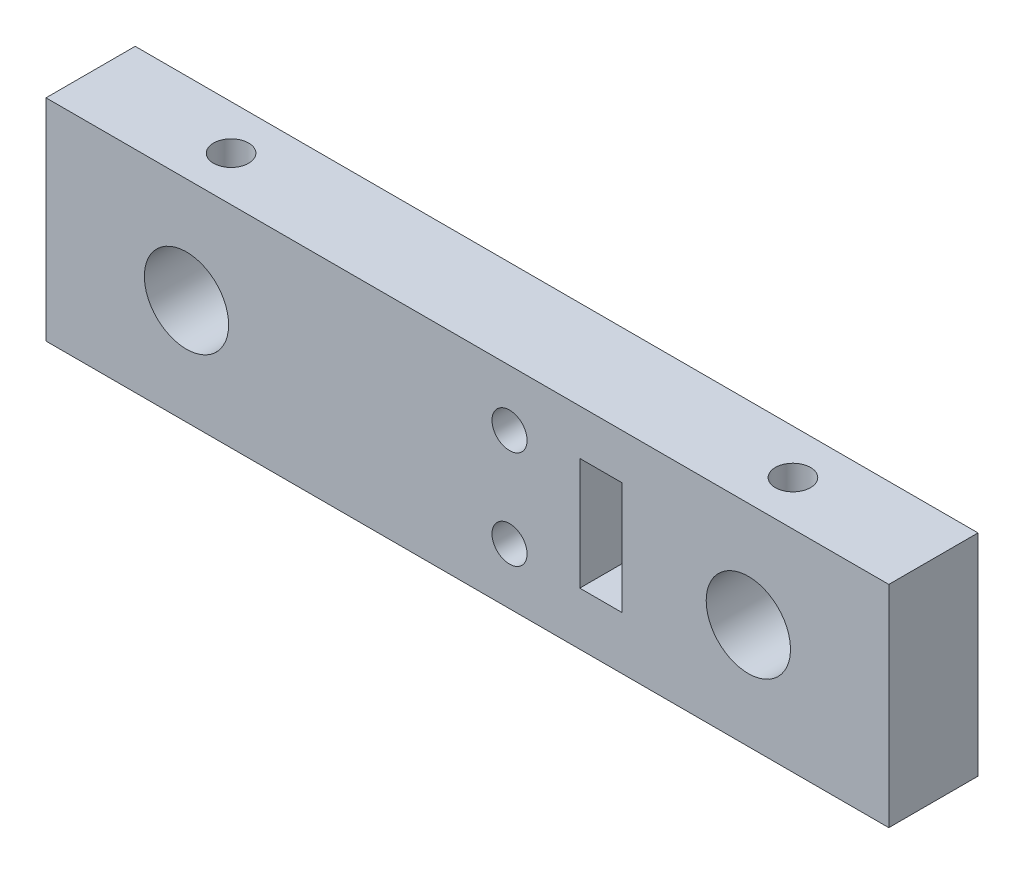
SolidWorks part; units mm, degrees
material "6061 Alloy"
ref_plane "Front Plane" through (0, 0, 0) normal (0, 0, 1) x (1, 0, 0)
ref_plane "Top Plane" through (0, 0, 0) normal (0, 1, 0) x (1, 0, 0)
ref_plane "Right Plane" through (0, 0, 0) normal (1, 0, 0) x (0, 0, -1)
sketch "Sketch1" plane through (0, 0, 0) normal (0, 0, 1) x (1, 0, 0)
  line L0 (30, 15) -> (30, 0) construction
  line L1 (0, 0) -> (60, 0)
  line L2 (0, 0) -> (0, 15)
  line L3 (0, 15) -> (60, 15)
  line L4 (60, 0) -> (60, 15)
  line L5 (0, 7.5) -> (60, 7.5) construction
  circle A0 centre (10, 7.5) radius 3
  circle A1 centre (50, 7.5) radius 3
  dimension "D3" = 6
  dimension "D1" = 60
  dimension "D2" = 15
  dimension "D4" = 40
extrude "Boss-Extrude1" add sketch "Sketch1" along normal blind 6.35
ref_axis "Axis1" through (10, 7.5, 6.35) along (0, 0, -1)
hole_wizard "M3 Tapped Hole1" positions "Sketch4" profile "Sketch3" tap size "M3" standard "ISO"
sketch "Sketch4" plane through (0, 15, 0) normal (0, 1, 0) x (-1, 0, 0)
  line L0 (0, 3.175) -> (-60, 3.175) construction
  line L1 (0, 6.35) -> (0, 0) construction
  line L2 (-60, 6.35) -> (-60, 0) construction
  line L5 (-30, 0) -> (-30, 6.35) construction
  line L6 (-60, 0) -> (0, 0) construction
  line L7 (-60, 6.35) -> (0, 6.35) construction
  line L10 (-10, 6.35) -> (-10, 0) construction
  point P0 (-10, 3.175)
  point P25 (-50, 3.175)
sketch "Sketch3" plane through (10, 15, 3.175) normal (1, 0, 0) x (0, 0, 1)
  line L0 (0, 0) -> (0, 9.2511)
  line L1 (0, 9.2511) -> (1.25, 8.5)
  line L2 (1.25, 8.5) -> (1.25, 0)
  line L5 (1.25, 0) -> (0, 0)
  line L10 (0, 9.2511) -> (-1.25, 8.5) construction
  line L11 (0, -6.35) -> (0, 107.95) construction
  dimension "Tap Drill Dia." = 2.5
  dimension "Tap Drill Depth" = 8.5
  dimension "Drill Angle" = 118
cosmetic thread "Hole Thread1" parameters "D1"=4.8642, "D2"=3
cosmetic thread "Hole Thread2" parameters "D1"=4.8642, "D2"=3
ref_plane "Center plane" through (30, 0, 0) normal (-1, 0, 0) x (0, 0, 1)
ref_plane "Belt plane" through (39, 0, 0) normal (1, 0, 0) x (0, 0, -1)
sketch "Sketch5" plane through (0, 0, 6.35) normal (0, 0, 1) x (1, 0, 0)
  line L1 (38, 11.7693) -> (41, 11.7693)
  line L2 (38, 11.7693) -> (38, 3.7693)
  line L3 (38, 3.7693) -> (41, 3.7693)
  line L4 (41, 11.7693) -> (41, 3.7693)
  line L5 (39, -3.4925) -> (39, 3.4925) construction
  dimension "D1" = 3
  dimension "D2" = 1
  dimension "D3" = 8
extrude "Cut-Extrude1" cut sketch "Sketch5" against normal through all
hole_wizard "M3 Tapped Hole2" positions "Sketch7" profile "Sketch8" tap size "M3" standard "ISO" end condition through all
sketch "Sketch7" plane through (0, 0, 6.35) normal (0, 0, 1) x (1, 0, 0)
  line L0 (60, 7.5) -> (28.002, 7.5) construction
  line L1 (60, 0) -> (60, 15) construction
  line L3 (33, 15) -> (33, 0) construction
  line L4 (60, 15) -> (0, 15) construction
  line L5 (0, 0) -> (60, 0) construction
  point P0 (33, 11)
  point P18 (33, 4)
  dimension "D1" = 27
  dimension "D2" = 7
sketch "Sketch8" plane through (33, 11, 6.35) normal (1, 0, 0) x (0, -1, 0)
  line L0 (0, 0) -> (0, 6.35)
  line L1 (0, 6.35) -> (1.25, 6.35)
  line L2 (1.25, 6.35) -> (1.25, 0)
  line L5 (1.25, 0) -> (0, 0)
  line L11 (0, -6.35) -> (0, 107.95) construction
  dimension "Thru Tap Drill Dia." = 2.5
  dimension "Thru Tap Drill Depth" = 6.35
cosmetic thread "Hole Thread3" parameters "D2"=3
cosmetic thread "Hole Thread4" parameters "D2"=3
